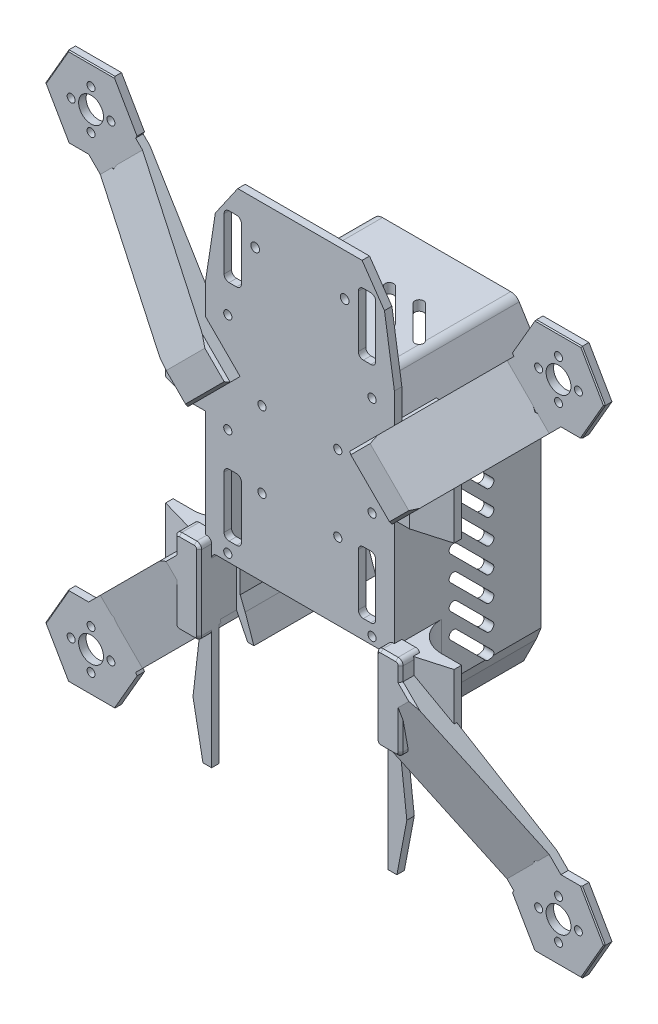
SolidWorks part; units mm, degrees
note: '?' marks a value the reader was unsure of.
material "镁合金_CNC_暂定1800kg_m3"
ref_plane "前视基准面" through (0, 0, 0) normal (0, 0, 1) x (1, 0, 0)
ref_plane "上视基准面" through (0, 0, 0) normal (0, 1, 0) x (1, 0, 0)
ref_plane "右视基准面" through (0, 0, 0) normal (1, 0, 0) x (0, 0, -1)
other "Configuration Table"
sketch "草图73" plane through (0, 0, 0) normal (0, 0, 1) x (1, 0, 0)
  line L17 (0, -118) -> (25, -114)
  line L18 (25, -114) -> (39, -101)
  line L19 (39, -101) -> (43, -80)
  line L20 (43, -80) -> (40, -54)
  line L21 (40, -54) -> (38, -32)
  line L22 (38, -32) -> (38, 67)
  line L23 (38, 67) -> (34, 93)
  line L24 (34, 93) -> (25, 106)
  line L25 (25, 106) -> (-25, 106)
  line L26 (-25, 106) -> (-34, 93)
  line L27 (-34, 93) -> (-38, 67)
  line L28 (-38, 67) -> (-38, -32)
  line L29 (-38, -32) -> (-40, -54)
  line L30 (-40, -54) -> (-43, -80)
  line L31 (-43, -80) -> (-39, -101)
  line L32 (-39, -101) -> (-25, -114)
  line L33 (-25, -114) -> (0, -118)
extrude "连续流线脊顶_三毫米基础" add sketch "草图73" along normal blind 3
sketch "草图85" plane through (0, 0, 0) normal (0, 0, 1) x (1, 0, 0)
  line L0 (-38, -60) -> (-38, 50)
  line L1 (-38, 50) -> (-28, 66)
  line L2 (-28, 66) -> (28, 66)
  line L3 (28, 66) -> (38, 50)
  line L4 (38, 50) -> (38, -60)
  line L5 (38, -60) -> (34, -60)
  line L6 (34, -60) -> (34, 48)
  line L7 (34, 48) -> (26, 62)
  line L8 (26, 62) -> (-26, 62)
  line L9 (-26, 62) -> (-34, 48)
  line L10 (-34, 48) -> (-34, -60)
  line L11 (-34, -60) -> (-38, -60)
extrude "机舱侧壁后壁与脊顶一体_4mm" add sketch "草图85" along normal blind 56 from offset 56
sketch "草图89" plane through (0, 0, 0) normal (0, 0, 1) x (1, 0, 0)
  line L0 (-36.5, -47.5) -> (-33, -47.5)
  line L1 (-31.5, -46) -> (-31.5, -40)
  line L2 (-33, -38.5) -> (-36.5, -38.5)
  line L3 (-38, -40) -> (-38, -46)
  arc A0 (-33, -47.5) -> (-31.5, -46) centre (-33, -46) ccw
  arc A1 (-31.5, -40) -> (-33, -38.5) centre (-33, -40) ccw
  arc A2 (-36.5, -38.5) -> (-38, -40) centre (-36.5, -40) ccw
  arc A3 (-38, -46) -> (-36.5, -47.5) centre (-36.5, -46) ccw
extrude "检修盖一体螺母台_-1_-1" add sketch "草图89" along normal blind 11 from offset 56
sketch "草图91" plane through (0, 0, 0) normal (0, 0, 1) x (1, 0, 0)
  line L0 (-36.5, 38.5) -> (-33, 38.5)
  line L1 (-31.5, 40) -> (-31.5, 46)
  line L2 (-33, 47.5) -> (-36.5, 47.5)
  line L3 (-38, 46) -> (-38, 40)
  arc A0 (-33, 38.5) -> (-31.5, 40) centre (-33, 40) ccw
  arc A1 (-31.5, 46) -> (-33, 47.5) centre (-33, 46) ccw
  arc A2 (-36.5, 47.5) -> (-38, 46) centre (-36.5, 46) ccw
  arc A3 (-38, 40) -> (-36.5, 38.5) centre (-36.5, 40) ccw
extrude "检修盖一体螺母台_-1_1" add sketch "草图91" along normal blind 11 from offset 56
sketch "草图93" plane through (0, 0, 0) normal (0, 0, 1) x (1, 0, 0)
  line L0 (33, -47.5) -> (36.5, -47.5)
  line L1 (38, -46) -> (38, -40)
  line L2 (36.5, -38.5) -> (33, -38.5)
  line L3 (31.5, -40) -> (31.5, -46)
  arc A0 (36.5, -47.5) -> (38, -46) centre (36.5, -46) ccw
  arc A1 (38, -40) -> (36.5, -38.5) centre (36.5, -40) ccw
  arc A2 (33, -38.5) -> (31.5, -40) centre (33, -40) ccw
  arc A3 (31.5, -46) -> (33, -47.5) centre (33, -46) ccw
extrude "检修盖一体螺母台_1_-1" add sketch "草图93" along normal blind 11 from offset 56
sketch "草图95" plane through (0, 0, 0) normal (0, 0, 1) x (1, 0, 0)
  line L0 (33, 38.5) -> (36.5, 38.5)
  line L1 (38, 40) -> (38, 46)
  line L2 (36.5, 47.5) -> (33, 47.5)
  line L3 (31.5, 46) -> (31.5, 40)
  arc A0 (36.5, 38.5) -> (38, 40) centre (36.5, 40) ccw
  arc A1 (38, 46) -> (36.5, 47.5) centre (36.5, 46) ccw
  arc A2 (33, 47.5) -> (31.5, 46) centre (33, 46) ccw
  arc A3 (31.5, 40) -> (33, 38.5) centre (33, 40) ccw
extrude "检修盖一体螺母台_1_1" add sketch "草图95" along normal blind 11 from offset 56
sketch "草图97" plane through (0, 0, 0) normal (0, 0, 1) x (1, 0, 0)
  circle A4 centre (-34, -43) radius 1.25
  circle A5 centre (-34, 43) radius 1.25
  circle A6 centre (34, -43) radius 1.25
  circle A7 centre (34, 43) radius 1.25
extrude "检修盖四M3螺纹底孔_深8" cut sketch "草图97" along normal blind 8 from offset 56
sketch "草图100" plane through (0, 0, 0) normal (0, 0, 1) x (1, 0, 0)
  line L76 (-28.5, -18.5) -> (-25.5, -18.5)
  line L77 (-23.5, -16.5) -> (-23.5, 4.5)
  line L78 (-25.5, 6.5) -> (-28.5, 6.5)
  line L79 (-30.5, 4.5) -> (-30.5, -16.5)
  line L80 (-28.5, 71.5) -> (-25.5, 71.5)
  line L81 (-23.5, 73.5) -> (-23.5, 94.5)
  line L82 (-25.5, 96.5) -> (-28.5, 96.5)
  line L83 (-30.5, 94.5) -> (-30.5, 73.5)
  line L84 (25.5, -18.5) -> (28.5, -18.5)
  line L85 (30.5, -16.5) -> (30.5, 4.5)
  line L86 (28.5, 6.5) -> (25.5, 6.5)
  line L87 (23.5, 4.5) -> (23.5, -16.5)
  line L88 (25.5, 71.5) -> (28.5, 71.5)
  line L89 (30.5, 73.5) -> (30.5, 94.5)
  line L90 (28.5, 96.5) -> (25.5, 96.5)
  line L91 (23.5, 94.5) -> (23.5, 73.5)
  arc A86 (-25.5, -18.5) -> (-23.5, -16.5) centre (-25.5, -16.5) ccw
  arc A87 (-23.5, 4.5) -> (-25.5, 6.5) centre (-25.5, 4.5) ccw
  arc A88 (-28.5, 6.5) -> (-30.5, 4.5) centre (-28.5, 4.5) ccw
  arc A89 (-30.5, -16.5) -> (-28.5, -18.5) centre (-28.5, -16.5) ccw
  arc A90 (-25.5, 71.5) -> (-23.5, 73.5) centre (-25.5, 73.5) ccw
  arc A91 (-23.5, 94.5) -> (-25.5, 96.5) centre (-25.5, 94.5) ccw
  arc A92 (-28.5, 96.5) -> (-30.5, 94.5) centre (-28.5, 94.5) ccw
  arc A93 (-30.5, 73.5) -> (-28.5, 71.5) centre (-28.5, 73.5) ccw
  arc A94 (28.5, -18.5) -> (30.5, -16.5) centre (28.5, -16.5) ccw
  arc A95 (30.5, 4.5) -> (28.5, 6.5) centre (28.5, 4.5) ccw
  arc A96 (25.5, 6.5) -> (23.5, 4.5) centre (25.5, 4.5) ccw
  arc A97 (23.5, -16.5) -> (25.5, -18.5) centre (25.5, -16.5) ccw
  arc A98 (28.5, 71.5) -> (30.5, 73.5) centre (28.5, 73.5) ccw
  arc A99 (30.5, 94.5) -> (28.5, 96.5) centre (28.5, 94.5) ccw
  arc A100 (25.5, 96.5) -> (23.5, 94.5) centre (25.5, 94.5) ccw
  arc A101 (23.5, 73.5) -> (25.5, 71.5) centre (25.5, 73.5) ccw
extrude "顶面扎带_导轨_XT30绝缘座孔" cut sketch "草图100" along normal blind 3
sketch "草图106" plane through (0, 0, 0) normal (0, 0, 1) x (1, 0, 0)
  line L6 (-31, -60) -> (-36, -50)
  line L7 (-36, -50) -> (-38, -45)
  line L8 (-38, -45) -> (-34, -45)
  line L9 (-34, -45) -> (-32, -50)
  line L10 (-32, -50) -> (-28.5, -60)
  line L11 (-28.5, -60) -> (-31, -60)
extrude "流线机舱前部内收壁_-1" add sketch "草图106" along normal blind 56 from offset 56
sketch "草图107" plane through (0, 0, 0) normal (0, 0, 1) x (1, 0, 0)
  line L0 (-31, -60) -> (-36, -50)
  line L1 (-36, -50) -> (-38, -45)
  line L2 (-38, -45) -> (-43, -45)
  line L3 (-43, -45) -> (-43, -63)
  line L4 (-43, -63) -> (-31, -63)
  line L5 (-31, -63) -> (-31, -60)
extrude "机头侧壁斜切_-1" cut sketch "草图107" along normal blind 56 from offset 56
sketch "草图108" plane through (0, 0, 0) normal (0, 0, 1) x (1, 0, 0)
  line L6 (31, -60) -> (36, -50)
  line L7 (36, -50) -> (38, -45)
  line L8 (38, -45) -> (34, -45)
  line L9 (34, -45) -> (32, -50)
  line L10 (32, -50) -> (28.5, -60)
  line L11 (28.5, -60) -> (31, -60)
extrude "流线机舱前部内收壁_1" add sketch "草图108" along normal blind 56 from offset 56
sketch "草图109" plane through (0, 0, 0) normal (0, 0, 1) x (1, 0, 0)
  line L0 (31, -60) -> (36, -50)
  line L1 (36, -50) -> (38, -45)
  line L2 (38, -45) -> (43, -45)
  line L3 (43, -45) -> (43, -63)
  line L4 (43, -63) -> (31, -63)
  line L5 (31, -63) -> (31, -60)
extrude "机头收腰避免桨盘包络" cut sketch "草图109" along normal blind 56 from offset 56
fillet "尾舱内角R2刀具过渡" radius 2 2 edges at (26, 62, -28) (-26, 62, -28)
fillet "尾舱外角R4流线过渡" radius 4 2 edges at (-28, 66, -28) (28, 66, -28)
sketch "草图113" plane through (0, 0, 0) normal (0, 0, 1) x (1, 0, 0)
  line L0 (-50, -159) -> (50, -159)
  line L1 (50, -159) -> (50, -101)
  line L2 (50, -101) -> (-50, -101)
  line L3 (-50, -101) -> (-50, -159)
extrude "机头端裁短以嵌入雷达" cut sketch "草图113" along normal blind 12
sketch "草图114" plane through (0, 0, 0) normal (0, 0, 1) x (1, 0, 0)
  line L0 (-33.5, -104) -> (33.5, -104)
  line L1 (35.5, -102) -> (35.5, -28)
  line L2 (33.5, -26) -> (-33.5, -26)
  line L3 (-35.5, -28) -> (-35.5, -102)
  arc A0 (33.5, -104) -> (35.5, -102) centre (33.5, -102) ccw
  arc A1 (35.5, -28) -> (33.5, -26) centre (33.5, -28) ccw
  arc A2 (-33.5, -26) -> (-35.5, -28) centre (-33.5, -28) ccw
  arc A3 (-35.5, -102) -> (-33.5, -104) centre (-33.5, -102) ccw
extrude "下沉雷达正下方走线开窗" cut sketch "草图114" along normal blind 17 from offset 7
sketch "草图115" plane through (0, 0, 0) normal (0, 0, 1) x (1, 0, 0)
  circle A0 centre (-15.25, 4.75) radius 1.65
  circle A1 centre (-15.25, 35.25) radius 1.65
  circle A2 centre (15.25, 4.75) radius 1.65
  circle A3 centre (15.25, 35.25) radius 1.65
extrude "倒置贴顶一体板四M3孔" cut sketch "草图115" along normal blind 3
sketch "草图116" plane through (0, 0, 0) normal (0, 0, 1) x (1, 0, 0)
  circle A4 centre (-29, -23) radius 1.65
  circle A5 centre (29, -23) radius 1.65
extrude "独立雷达座后双M3固定孔" cut sketch "草图116" along normal blind 3
sketch "草图117" plane through (0, 0, 0) normal (1, 0, 0) x (0, 0, -1)
  line L0 (36.4853, -43.0104) -> (21.9896, -28.5147)
  line L1 (19.5147, -30.9896) -> (34.0104, -45.4853)
  line L2 (36.4853, -33.0104) -> (21.9896, -18.5147)
  line L3 (19.5147, -20.9896) -> (34.0104, -35.4853)
  line L4 (36.4853, -23.0104) -> (21.9896, -8.5147)
  line L5 (19.5147, -10.9896) -> (34.0104, -25.4853)
  line L6 (36.4853, -13.0104) -> (21.9896, 1.4853)
  line L7 (19.5147, -0.9896) -> (34.0104, -15.4853)
  line L8 (36.4853, -3.0104) -> (21.9896, 11.4853)
  line L9 (19.5147, 9.0104) -> (34.0104, -5.4853)
  line L10 (36.4853, 6.9896) -> (21.9896, 21.4853)
  line L11 (19.5147, 19.0104) -> (34.0104, 4.5147)
  line L12 (36.4853, 16.9896) -> (21.9896, 31.4853)
  line L13 (19.5147, 29.0104) -> (34.0104, 14.5147)
  line L14 (36.4853, 26.9896) -> (21.9896, 41.4853)
  line L15 (19.5147, 39.0104) -> (34.0104, 24.5147)
  line L16 (36.4853, 36.9896) -> (21.9896, 51.4853)
  line L17 (19.5147, 49.0104) -> (34.0104, 34.5147)
  arc A0 (21.9896, -28.5147) -> (19.5147, -30.9896) centre (20.7522, -29.7522) ccw
  arc A1 (34.0104, -45.4853) -> (36.4853, -43.0104) centre (35.2478, -44.2478) ccw
  arc A2 (21.9896, -18.5147) -> (19.5147, -20.9896) centre (20.7522, -19.7522) ccw
  arc A3 (34.0104, -35.4853) -> (36.4853, -33.0104) centre (35.2478, -34.2478) ccw
  arc A4 (21.9896, -8.5147) -> (19.5147, -10.9896) centre (20.7522, -9.7522) ccw
  arc A5 (34.0104, -25.4853) -> (36.4853, -23.0104) centre (35.2478, -24.2478) ccw
  arc A6 (21.9896, 1.4853) -> (19.5147, -0.9896) centre (20.7522, 0.2478) ccw
  arc A7 (34.0104, -15.4853) -> (36.4853, -13.0104) centre (35.2478, -14.2478) ccw
  arc A8 (21.9896, 11.4853) -> (19.5147, 9.0104) centre (20.7522, 10.2478) ccw
  arc A9 (34.0104, -5.4853) -> (36.4853, -3.0104) centre (35.2478, -4.2478) ccw
  arc A10 (21.9896, 21.4853) -> (19.5147, 19.0104) centre (20.7522, 20.2478) ccw
  arc A11 (34.0104, 4.5147) -> (36.4853, 6.9896) centre (35.2478, 5.7522) ccw
  arc A12 (21.9896, 31.4853) -> (19.5147, 29.0104) centre (20.7522, 30.2478) ccw
  arc A13 (34.0104, 14.5147) -> (36.4853, 16.9896) centre (35.2478, 15.7522) ccw
  arc A14 (21.9896, 41.4853) -> (19.5147, 39.0104) centre (20.7522, 40.2478) ccw
  arc A15 (34.0104, 24.5147) -> (36.4853, 26.9896) centre (35.2478, 25.7522) ccw
  arc A16 (21.9896, 51.4853) -> (19.5147, 49.0104) centre (20.7522, 50.2478) ccw
  arc A17 (34.0104, 34.5147) -> (36.4853, 36.9896) centre (35.2478, 35.7522) ccw
extrude "双侧短槽45度平行排布" cut sketch "草图117" along normal blind 80 and the other way blind 80
sketch "草图118" plane through (0, 0, 0) normal (0, 1, 0) x (1, 0, 0)
  line L0 (-23.3033, 34.7782) -> (-10.2218, 21.6967)
  line L1 (-12.6967, 19.2218) -> (-25.7782, 32.3033)
  line L2 (-11.3033, 34.7782) -> (1.7782, 21.6967)
  line L3 (-0.6967, 19.2218) -> (-13.7782, 32.3033)
  line L4 (0.6967, 34.7782) -> (13.7782, 21.6967)
  line L5 (11.3033, 19.2218) -> (-1.7782, 32.3033)
  line L6 (12.6967, 34.7782) -> (25.7782, 21.6967)
  line L7 (23.3033, 19.2218) -> (10.2218, 32.3033)
  arc A0 (-10.2218, 21.6967) -> (-12.6967, 19.2218) centre (-11.4593, 20.4593) cw
  arc A1 (-25.7782, 32.3033) -> (-23.3033, 34.7782) centre (-24.5407, 33.5407) cw
  arc A2 (1.7782, 21.6967) -> (-0.6967, 19.2218) centre (0.5407, 20.4593) cw
  arc A3 (-13.7782, 32.3033) -> (-11.3033, 34.7782) centre (-12.5407, 33.5407) cw
  arc A4 (13.7782, 21.6967) -> (11.3033, 19.2218) centre (12.5407, 20.4593) cw
  arc A5 (-1.7782, 32.3033) -> (0.6967, 34.7782) centre (-0.5407, 33.5407) cw
  arc A6 (25.7782, 21.6967) -> (23.3033, 19.2218) centre (24.5407, 20.4593) cw
  arc A7 (10.2218, 32.3033) -> (12.6967, 34.7782) centre (11.4593, 33.5407) cw
extrude "尾壁短槽45度平行排布" cut sketch "草图118" along normal blind 12 and the other way blind 12 from offset 60
ref_axis "下倾机臂共用中心Z轴" through (0, 0, -59.2) along (0, 0, 1)?
ref_plane "下倾机臂侧截面_0" through (0, 0, 0) normal (-0.7071, 0.7071, 0) x (0, 0, 1)
sketch "草图119" plane through (0, 0, 0) normal (-0.7071, 0.7071, 0) x (0, 0, 1)
  line L8 (0, -46) -> (0, -58)
  line L9 (0, -58) -> (-10, -115.6569)
  line L10 (-10, -115.6569) -> (-10, -133.6569)
  line L11 (-10, -133.6569) -> (-7, -133.6569)
  line L12 (-7, -133.6569) -> (-7, -115.6569)
  line L13 (-7, -115.6569) -> (8, -58)
  line L14 (8, -58) -> (8, -46)
  line L15 (8, -46) -> (0, -46)
extrude "连续下倾10mm变截面机臂_0_-1" add sketch "草图119" along normal blind 24 from offset 12
sketch "草图120" plane through (0, 0, 0) normal (-0.7071, 0.7071, 0) x (0, 0, 1)
  line L8 (0, 46) -> (0, 58)
  line L9 (0, 58) -> (-10, 115.6569)
  line L10 (-10, 115.6569) -> (-10, 133.6569)
  line L11 (-10, 133.6569) -> (-7, 133.6569)
  line L12 (-7, 133.6569) -> (-7, 115.6569)
  line L13 (-7, 115.6569) -> (8, 58)
  line L14 (8, 58) -> (8, 46)
  line L15 (8, 46) -> (0, 46)
extrude "连续下倾10mm变截面机臂_0_1" add sketch "草图120" along normal blind 24 from offset 12
ref_plane "下倾机臂侧截面_1" through (0, 0, 0) normal (-0.7071, -0.7071, 0) x (0, 0, 1)
sketch "草图121" plane through (0, 0, 0) normal (-0.7071, -0.7071, 0) x (0, 0, 1)
  line L8 (0, 46) -> (0, 58)
  line L9 (0, 58) -> (-10, 115.6569)
  line L10 (-10, 115.6569) -> (-10, 133.6569)
  line L11 (-10, 133.6569) -> (-7, 133.6569)
  line L12 (-7, 133.6569) -> (-7, 115.6569)
  line L13 (-7, 115.6569) -> (8, 58)
  line L14 (8, 58) -> (8, 46)
  line L15 (8, 46) -> (0, 46)
extrude "连续下倾10mm变截面机臂_1_-1" add sketch "草图121" along normal blind 24 from offset 12
sketch "草图122" plane through (0, 0, 0) normal (-0.7071, -0.7071, 0) x (0, 0, 1)
  line L8 (0, -46) -> (0, -58)
  line L9 (0, -58) -> (-10, -115.6569)
  line L10 (-10, -115.6569) -> (-10, -133.6569)
  line L11 (-10, -133.6569) -> (-7, -133.6569)
  line L12 (-7, -133.6569) -> (-7, -115.6569)
  line L13 (-7, -115.6569) -> (8, -58)
  line L14 (8, -58) -> (8, -46)
  line L15 (8, -46) -> (0, -46)
extrude "连续下倾10mm变截面机臂_1_1" add sketch "草图122" along normal blind 24 from offset 12
sketch "草图123" plane through (0, 0, 0) normal (0, 0, 1) x (1, 0, 0)
  line L0 (-43.5, -55) -> (-37.5, -55)
  line L1 (-35.5, -53) -> (-35.5, -23)
  line L2 (-37.5, -21) -> (-43.5, -21)
  line L3 (-45.5, -23) -> (-45.5, -53)
  arc A0 (-37.5, -55) -> (-35.5, -53) centre (-37.5, -53) ccw
  arc A1 (-35.5, -23) -> (-37.5, -21) centre (-37.5, -23) ccw
  arc A2 (-43.5, -21) -> (-45.5, -23) centre (-43.5, -23) ccw
  arc A3 (-45.5, -53) -> (-43.5, -55) centre (-43.5, -53) ccw
extrude "前臂开窗外侧整体加强梁_-1" add sketch "草图123" along normal blind 8
sketch "草图124" plane through (0, 0, 0) normal (0, 0, 1) x (1, 0, 0)
  line L0 (37.5, -55) -> (43.5, -55)
  line L1 (45.5, -53) -> (45.5, -23)
  line L2 (43.5, -21) -> (37.5, -21)
  line L3 (35.5, -23) -> (35.5, -53)
  arc A0 (43.5, -55) -> (45.5, -53) centre (43.5, -53) ccw
  arc A1 (45.5, -23) -> (43.5, -21) centre (43.5, -23) ccw
  arc A2 (37.5, -21) -> (35.5, -23) centre (37.5, -23) ccw
  arc A3 (35.5, -53) -> (37.5, -55) centre (37.5, -53) ccw
extrude "前臂开窗外侧整体加强梁_1" add sketch "草图124" along normal blind 8
sketch "草图125" plane through (0, 0, 0) normal (0, 0, 1) x (1, 0, 0)
  line L0 (-33.5, -104) -> (33.5, -104)
  line L1 (35.5, -102) -> (35.5, -28)
  line L2 (33.5, -26) -> (-33.5, -26)
  line L3 (-35.5, -28) -> (-35.5, -102)
  arc A0 (33.5, -104) -> (35.5, -102) centre (33.5, -102) ccw
  arc A1 (35.5, -28) -> (33.5, -26) centre (33.5, -28) ccw
  arc A2 (-33.5, -26) -> (-35.5, -28) centre (-33.5, -28) ccw
  arc A3 (-35.5, -102) -> (-33.5, -104) centre (-33.5, -102) ccw
extrude "下倾前臂保持雷达及走线净空" cut sketch "草图125" along normal blind 19 from offset 7
sketch "草图126" plane through (0, 0, 0) normal (0, 0, 1) x (1, 0, 0)
  line L6 (-75.5, -94) -> (-84.75, -77.9785)
  line L7 (-84.75, -77.9785) -> (-103.25, -77.9785)
  line L8 (-103.25, -77.9785) -> (-112.5, -94)
  line L9 (-112.5, -94) -> (-103.25, -110.0215)
  line L10 (-103.25, -110.0215) -> (-84.75, -110.0215)
  line L11 (-84.75, -110.0215) -> (-75.5, -94)
extrude "正六边形电机安装台_-1_-1" add sketch "草图126" along normal blind 3 from offset 10
sketch "草图127" plane through (0, 0, 0) normal (0, 0, 1) x (1, 0, 0)
  line L6 (-75.5, 94) -> (-84.75, 110.0215)
  line L7 (-84.75, 110.0215) -> (-103.25, 110.0215)
  line L8 (-103.25, 110.0215) -> (-112.5, 94)
  line L9 (-112.5, 94) -> (-103.25, 77.9785)
  line L10 (-103.25, 77.9785) -> (-84.75, 77.9785)
  line L11 (-84.75, 77.9785) -> (-75.5, 94)
extrude "正六边形电机安装台_-1_1" add sketch "草图127" along normal blind 3 from offset 10
sketch "草图128" plane through (0, 0, 0) normal (0, 0, 1) x (1, 0, 0)
  line L6 (112.5, -94) -> (103.25, -77.9785)
  line L7 (103.25, -77.9785) -> (84.75, -77.9785)
  line L8 (84.75, -77.9785) -> (75.5, -94)
  line L9 (75.5, -94) -> (84.75, -110.0215)
  line L10 (84.75, -110.0215) -> (103.25, -110.0215)
  line L11 (103.25, -110.0215) -> (112.5, -94)
extrude "正六边形电机安装台_1_-1" add sketch "草图128" along normal blind 3 from offset 10
sketch "草图129" plane through (0, 0, 0) normal (0, 0, 1) x (1, 0, 0)
  line L6 (112.5, 94) -> (103.25, 110.0215)
  line L7 (103.25, 110.0215) -> (84.75, 110.0215)
  line L8 (84.75, 110.0215) -> (75.5, 94)
  line L9 (75.5, 94) -> (84.75, 77.9785)
  line L10 (84.75, 77.9785) -> (103.25, 77.9785)
  line L11 (103.25, 77.9785) -> (112.5, 94)
extrude "正六边形电机安装台_1_1" add sketch "草图129" along normal blind 3 from offset 10
sketch "草图130" plane through (0, 0, 0) normal (0, 0, 1) x (1, 0, 0)
  line L24 (-75.5, -94) -> (-84.75, -77.9785)
  line L25 (-84.75, -77.9785) -> (-103.25, -77.9785)
  line L26 (-103.25, -77.9785) -> (-112.5, -94)
  line L27 (-112.5, -94) -> (-103.25, -110.0215)
  line L28 (-103.25, -110.0215) -> (-84.75, -110.0215)
  line L29 (-84.75, -110.0215) -> (-75.5, -94)
  line L30 (-75.5, 94) -> (-84.75, 110.0215)
  line L31 (-84.75, 110.0215) -> (-103.25, 110.0215)
  line L32 (-103.25, 110.0215) -> (-112.5, 94)
  line L33 (-112.5, 94) -> (-103.25, 77.9785)
  line L34 (-103.25, 77.9785) -> (-84.75, 77.9785)
  line L35 (-84.75, 77.9785) -> (-75.5, 94)
  line L36 (112.5, -94) -> (103.25, -77.9785)
  line L37 (103.25, -77.9785) -> (84.75, -77.9785)
  line L38 (84.75, -77.9785) -> (75.5, -94)
  line L39 (75.5, -94) -> (84.75, -110.0215)
  line L40 (84.75, -110.0215) -> (103.25, -110.0215)
  line L41 (103.25, -110.0215) -> (112.5, -94)
  line L42 (112.5, 94) -> (103.25, 110.0215)
  line L43 (103.25, 110.0215) -> (84.75, 110.0215)
  line L44 (84.75, 110.0215) -> (75.5, 94)
  line L45 (75.5, 94) -> (84.75, 77.9785)
  line L46 (84.75, 77.9785) -> (103.25, 77.9785)
  line L47 (103.25, 77.9785) -> (112.5, 94)
extrude "六边形安装台顶面统一找平" cut sketch "草图130" along normal blind 20 from offset 7
sketch "草图131" plane through (0, 0, 0) normal (0, 0, 1) x (1, 0, 0)
  circle A20 centre (-94, -94) radius 5
  circle A21 centre (-102, -94) radius 1.6
  circle A22 centre (-94, -102) radius 1.6
  circle A23 centre (-86, -94) radius 1.6
  circle A24 centre (-94, -86) radius 1.6
  circle A25 centre (-94, 94) radius 5
  circle A26 centre (-102, 94) radius 1.6
  circle A27 centre (-94, 86) radius 1.6
  circle A28 centre (-86, 94) radius 1.6
  circle A29 centre (-94, 102) radius 1.6
  circle A30 centre (94, -94) radius 5
  circle A31 centre (86, -94) radius 1.6
  circle A32 centre (94, -102) radius 1.6
  circle A33 centre (102, -94) radius 1.6
  circle A34 centre (94, -86) radius 1.6
  circle A35 centre (94, 94) radius 5
  circle A36 centre (86, 94) radius 1.6
  circle A37 centre (94, 86) radius 1.6
  circle A38 centre (102, 94) radius 1.6
  circle A39 centre (94, 102) radius 1.6
extrude "下倾六边形电机台_最终四组安装孔" cut sketch "草图131" along normal blind 12 from offset 14
sketch "草图132" plane through (0, 0, 0) normal (0, 0, 1) x (1, 0, 0)
  circle A0 centre (-29, 20) radius 1.65
  circle A1 centre (-29, 60) radius 1.65
  circle A2 centre (29, 20) radius 1.65
  circle A3 centre (29, 60) radius 1.65
extrude "后抽电池仓四M3固定孔" cut sketch "草图132" along normal blind 3
sketch "草图133" plane through (0, 0, 0) normal (0, 0, 1) x (1, 0, 0)
  circle A0 centre (-18, 89) radius 1.75
  circle A1 centre (18, 89) radius 1.75
extrude "换电后盖下定位销孔" cut sketch "草图133" along normal blind 3
sketch "草图134" plane through (0, 0, 0) normal (0, 0, 1) x (1, 0, 0)
  circle A0 centre (-29, 60) radius 3.6
  circle A1 centre (29, 60) radius 3.6
extrude "电池仓后螺母局部内壁沉腔" cut sketch "草图134" along normal blind 3 from offset 3
sketch "草图136" plane through (0, 0, 0) normal (0, 1, 0) x (1, 0, 0)
  line L0 (-35.8, -3) -> (-44, -3)
  line L1 (-44, -3) -> (-58, 1)
  line L2 (-58, 1) -> (-58, 4)
  line L3 (-58, 4) -> (-50, 4)
  line L4 (-38, 16) -> (-35.8, 16)
  line L5 (-35.8, 16) -> (-35.8, -3)
  arc A0 (-50, 4) -> (-38, 16) centre (-50, 16) ccw
extrude "舱臂连续承力肩_R12_-1_-1" add sketch "草图136" along normal blind 32 from offset 54
sketch "草图137" plane through (0, 0, 0) normal (0, 1, 0) x (1, 0, 0)
  line L0 (-35.8, -3) -> (-44, -3)
  line L1 (-44, -3) -> (-58, 1)
  line L2 (-58, 1) -> (-58, 4)
  line L3 (-58, 4) -> (-50, 4)
  line L4 (-38, 16) -> (-35.8, 16)
  line L5 (-35.8, 16) -> (-35.8, -3)
  arc A0 (-50, 4) -> (-38, 16) centre (-50, 16) ccw
extrude "舱臂连续承力肩_R12_-1_1" add sketch "草图137" along normal blind 32 from offset 22
sketch "草图138" plane through (0, 0, 0) normal (0, 1, 0) x (1, 0, 0)
  line L0 (35.8, -3) -> (44, -3)
  line L1 (44, -3) -> (58, 1)
  line L2 (58, 1) -> (58, 4)
  line L3 (58, 4) -> (50, 4)
  line L4 (38, 16) -> (35.8, 16)
  line L5 (35.8, 16) -> (35.8, -3)
  arc A0 (50, 4) -> (38, 16) centre (50, 16) cw
extrude "舱臂连续承力肩_R12_1_-1" add sketch "草图138" along normal blind 32 from offset 54
sketch "草图139" plane through (0, 0, 0) normal (0, 1, 0) x (1, 0, 0)
  line L0 (35.8, -3) -> (44, -3)
  line L1 (44, -3) -> (58, 1)
  line L2 (58, 1) -> (58, 4)
  line L3 (58, 4) -> (50, 4)
  line L4 (38, 16) -> (35.8, 16)
  line L5 (35.8, 16) -> (35.8, -3)
  arc A0 (50, 4) -> (38, 16) centre (50, 16) cw
extrude "舱臂连续承力肩_R12_1_1" add sketch "草图139" along normal blind 32 from offset 22
chamfer "六边形电机台外缘倒角_C0p4" distance 0.4 angle 45 12 edges at (107.875, 85.9893, -7) (107.875, 102.0107, -7) (94, 110.0215, -7) (107.875, -85.9893, -7) (107.875, -102.0107, -7) (94, -110.0215, -7) (-94, 110.0215, -7) (-107.875, 102.0107, -7) (-107.875, 85.9893, -7) (-107.875, -85.9893, -7) (-107.875, -102.0107, -7) (-94, -110.0215, -7)
chamfer "四机臂根部整边倒角_C1" distance 1 angle 45 26 edges at (40.5, -55, 8) (45.5, -44.7622, 8) (40.5, -21, 8) (35.5, -38, 8) (-40.5, -55, 8) (-35.5, -38, 8) (-40.5, -21, 8) (-45.5, -44.7622, 8) (44.9142, -54.4142, 8) (36.0858, -54.4142, 8) (36.0858, -21.5858, 8) (44.9142, -21.5858, 8) (45.5, -25.7647, 8) (47.4987, -30.5282, 8) (-28.2843, 45.2548, 8) (-45.2548, 28.2843, 8) (-32.5269, 32.5269, 8) (45.2548, 28.2843, 8) (28.2843, 45.2548, 8) (32.5269, 32.5269, 8) (-44.9142, -54.4142, 8) (-36.0858, -54.4142, 8) (-36.0858, -21.5858, 8) (-44.9142, -21.5858, 8) (-45.5, -25.7647, 8) (-47.4987, -30.5282, 8)
